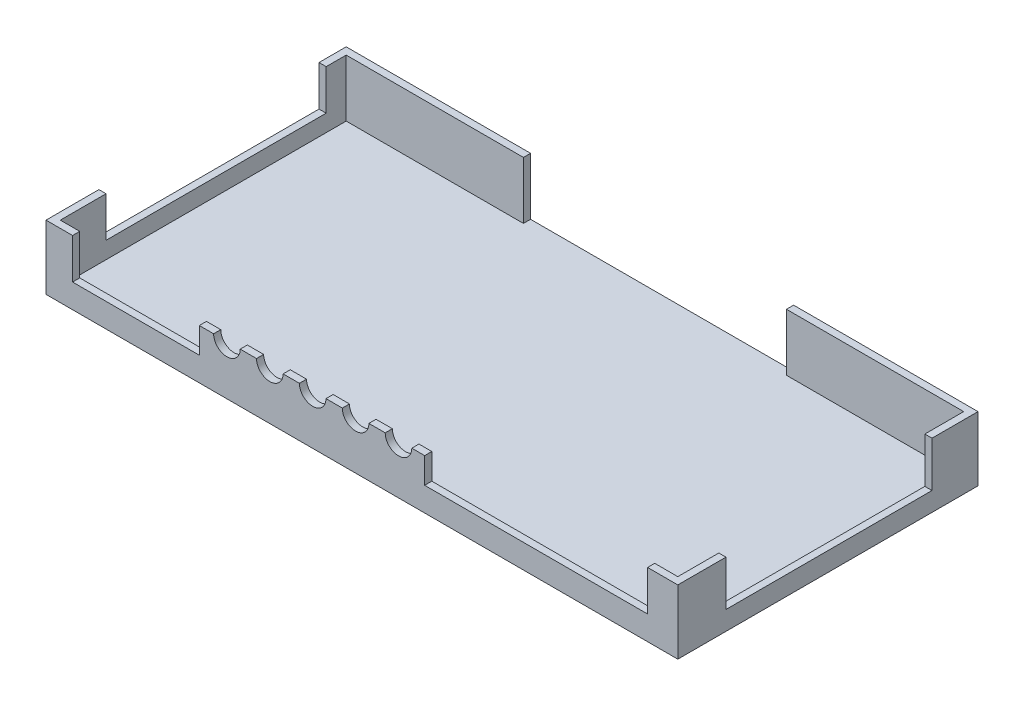
SolidWorks part; units mm, degrees
ref_plane "Front Plane" through (0, 0, 0) normal (0, 0, 1) x (1, 0, 0)
ref_plane "Top Plane" through (0, 0, 0) normal (0, 1, 0) x (1, 0, 0)
ref_plane "Right Plane" through (0, 0, 0) normal (1, 0, 0) x (0, 0, -1)
sketch "Sketch1" plane through (0, 0, 0) normal (0, 1, 0) x (1, 0, 0)
  line L0 (-110.5, -52.5) -> (-110.5, 52.5)
  line L1 (-108, -50) -> (108, -50)
  line L2 (-108, -50) -> (-108, 50)
  line L3 (-108, 50) -> (108, 50)
  line L4 (108, -50) -> (108, 50)
  line L5 (-108, -50) -> (108, 50) construction
  line L6 (-108, 50) -> (108, -50) construction
  line L7 (-110.5, 52.5) -> (110.5, 52.5)
  line L8 (110.5, -52.5) -> (110.5, 52.5)
  line L9 (-110.5, -52.5) -> (110.5, -52.5)
  point P0 (0, 0)
  dimension "D1" = 216
  dimension "D2" = 100
  dimension "D3" = 2.5
extrude "Boss-Extrude1" add sketch "Sketch1" along normal blind 20 contours L0 L9 L8 L7 L4 L1 L2 L3 region at (-108.0532, 0, 0)
extrude "Boss-Extrude2" add sketch "Sketch1<3>" against normal blind 2.5 contours L0 L7 L8 L9
sketch "Sketch1<3>" plane through (0, 0, 0) normal (0, 1, 0) x (1, 0, 0) same geometry as "Sketch1"
ref_plane "Plane1" through (-110.5, 20, 52.5) normal (1, 0, 0) x (0, 0, -1)
sketch "Sketch3" plane through (0, 0, 52.5) normal (0, 0, 1) x (1, 0, 0)
  line L0 (-110.5, 20) -> (110.5, 20) construction
  line L1 (-101.2008, 20) -> (99.9204, 20)
  line L2 (-101.2008, 20) -> (-101.2008, 5.8947)
  line L3 (-101.2008, 5.8947) -> (99.9204, 5.8947)
  line L4 (99.9204, 20) -> (99.9204, 5.8947)
extrude "Cut-Extrude1" cut sketch "Sketch3" against normal blind 10
sketch "Sketch4" plane through (110.5, 0, 0) normal (1, 0, 0) x (0, 0, -1)
  line L0 (-52.5, 20) -> (52.5, 20) construction
  line L1 (-35.6625, 20) -> (36.407, 20)
  line L2 (-35.6625, 20) -> (-35.6625, 4.1415)
  line L3 (-35.6625, 4.1415) -> (36.407, 4.1415)
  line L4 (36.407, 20) -> (36.407, 4.1415)
extrude "Cut-Extrude2" cut sketch "Sketch4" against normal blind 10
sketch "Sketch5" plane through (0, 0, 52.5) normal (0, 0, 1) x (1, 0, 0)
  line L0 (-144.165, 14.8947) -> (142.8743, 14.8947) construction
  line L1 (-101.2008, 5.8947) -> (99.9204, 5.8947) construction
  line L2 (0, -55) -> (0, 55) construction
  line L4 (-56.87, 5.8947) -> (21.95, 5.8947)
  line L6 (-42.57, 14.8947) -> (-36.87, 14.8947)
  line L7 (-27.57, 14.8947) -> (-21.87, 14.8947)
  line L8 (-12.57, 14.8947) -> (-6.86, 14.8947)
  line L9 (2.44, 14.8947) -> (8.15, 14.8947)
  line L10 (-56.87, 14.8947) -> (-56.87, 5.8947)
  line L11 (-56.87, 14.8947) -> (-51.87, 14.8947)
  line L12 (21.95, 14.8947) -> (21.95, 5.8947)
  line L13 (17.45, 14.8947) -> (21.95, 14.8947)
  circle A0 centre (-47.22, 14.8947) radius 4.65 construction
  circle A1 centre (-32.22, 14.8947) radius 4.65 construction
  circle A2 centre (-17.22, 14.8947) radius 4.65 construction
  circle A3 centre (-2.21, 14.8947) radius 4.65 construction
  circle A4 centre (12.8, 14.8947) radius 4.65 construction
  arc A5 (-51.87, 14.8947) -> (-42.57, 14.8947) centre (-47.22, 14.8947) ccw
  arc A6 (-36.87, 14.8947) -> (-27.57, 14.8947) centre (-32.22, 14.8947) ccw
  arc A7 (-21.87, 14.8947) -> (-12.57, 14.8947) centre (-17.22, 14.8947) ccw
  arc A8 (-6.86, 14.8947) -> (2.44, 14.8947) centre (-2.21, 14.8947) ccw
  arc A9 (8.15, 14.8947) -> (17.45, 14.8947) centre (12.8, 14.8947) ccw
  point P4 (-47.22, 14.8947)
  point P5 (-32.22, 14.8947)
  point P6 (-17.22, 14.8947)
  point P7 (-2.21, 14.8947)
  point P8 (12.8, 14.8947)
  dimension "D7" = 9.3
  dimension "D8" = 5
  dimension "D9" = 4.5
  dimension "D1" = 9
  dimension "D2" = 47.22
  dimension "D3" = 32.22
  dimension "D4" = 17.22
  dimension "D5" = 2.21
  dimension "D6" = 12.8
extrude "Boss-Extrude3" add sketch "Sketch5" against normal up to surface (2.5 mm away) up to face at (-0.3201, 11.4737, 50)
sketch "Sketch6" plane through (0, 0, -52.5) normal (0, 0, -1) x (-1, 0, 0)
  line L0 (110.5, 20) -> (-110.5, 20) construction
  line L1 (-46, 20) -> (46, 20)
  line L2 (-46, 20) -> (-46, 0)
  line L3 (-46, 0) -> (46, 0)
  line L4 (46, 20) -> (46, 0)
  line L5 (0, 55) -> (0, -55) construction
  dimension "D1" = 92
  dimension "D2" = 46
  dimension "D3" = 20
extrude "Cut-Extrude3" cut sketch "Sketch6" against normal blind 10
sketch "Sketch7" plane through (-110.5, 0, 0) normal (-1, 0, 0) x (0, 0, 1)
  line L0 (52.5, 20) -> (-52.5, 20) construction
  line L1 (34, 20) -> (-43, 20)
  line L2 (34, 20) -> (34, 5.9)
  line L3 (34, 5.9) -> (-43, 5.9)
  line L4 (-43, 20) -> (-43, 5.9)
  line L5 (52.5, 20) -> (52.5, -2.5) construction
  line L6 (52.5, -2.5) -> (-52.5, -2.5) construction
  dimension "D1" = 18.5
  dimension "D2" = 7
  dimension "D3" = 8.4
extrude "Cut-Extrude4" cut sketch "Sketch7" against normal blind 10
equation "\"D2@Sketch6\"=\"D1@Sketch6\"/2"
